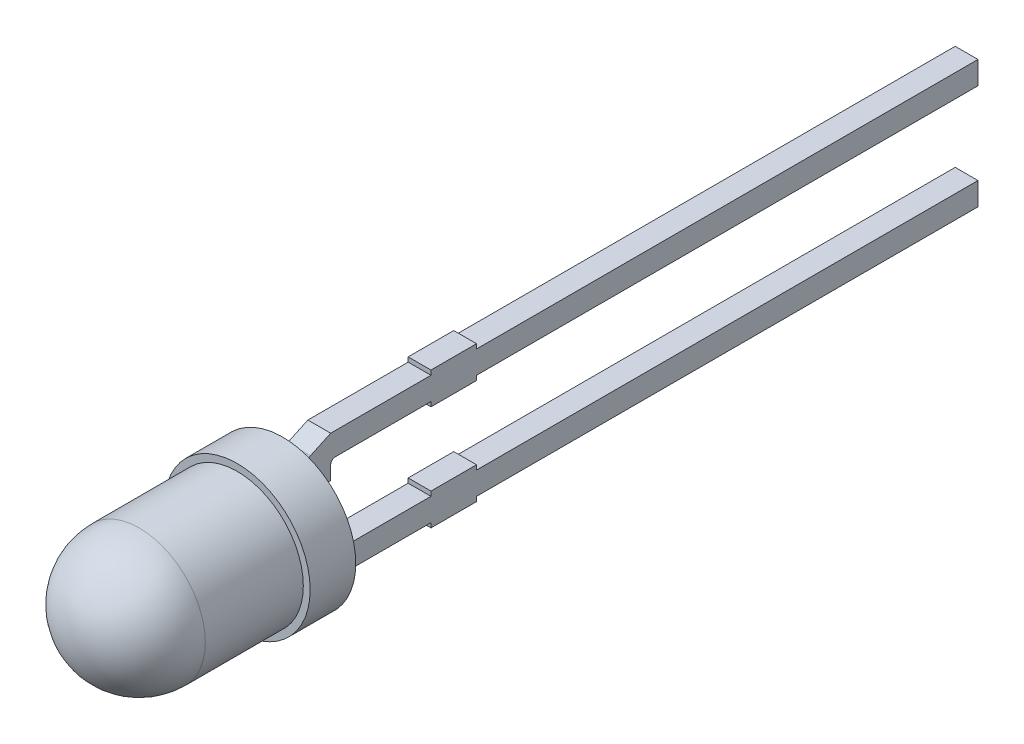
SolidWorks part; units mm, degrees
ref_plane "Front" through (0, 0, 0) normal (0, 0, 1) x (1, 0, 0)
ref_plane "Top" through (0, 0, 0) normal (0, 1, 0) x (1, 0, 0)
ref_plane "Right" through (0, 0, 0) normal (1, 0, 0) x (0, 0, -1)
sketch "Sketch1" plane through (0, 0, 0) normal (1, 0, 0) x (0, 0, -1)
  line L0 (0, 0) -> (76.2974, 0) construction
  line L1 (0, 1.45) -> (2.15, 1.45)
  line L2 (2.15, 1.45) -> (2.15, 1.6)
  line L3 (2.15, 1.6) -> (3.15, 1.6)
  line L4 (3.15, 1.6) -> (3.15, 0)
  line L5 (3.15, 0) -> (-1.45, 0)
  arc A0 (0, 1.45) -> (-1.45, 0) centre (0, 0) ccw
  dimension "D1" = 1.45
  dimension "D2" = 4.6
  dimension "D3" = 1
  dimension "D4" = 1.6
revolve "Revolve1" add sketch "Sketch1" angle 360 about L0
sketch "Sketch2" plane through (0, 0, 0) normal (1, 0, 0) x (0, 0, -1)
  line L0 (3.15, -1.6) -> (3.15, 1.6) construction
  line L1 (3.15, -1.6) -> (3.15, 1.6) construction
  line L2 (3.15, 1.027) -> (3.95, 1.4)
  line L3 (3.95, 1.4) -> (6.15, 1.4)
  line L4 (6.15, 1.4) -> (6.15, 1.5)
  line L5 (6.15, 1.5) -> (7.15, 1.5)
  line L6 (7.15, 1.5) -> (7.15, 1.4)
  line L7 (7.15, 1.4) -> (30.15, 1.4)
  line L8 (30.15, 1.4) -> (30.15, 0.9)
  line L9 (30.15, 0.9) -> (7.15, 0.9)
  line L10 (7.15, 0.9) -> (7.15, 0.8)
  line L11 (7.15, 0.8) -> (6.15, 0.8)
  line L12 (6.15, 0.8) -> (6.15, 0.9)
  line L13 (6.15, 0.9) -> (4.05, 0.9)
  line L14 (3.95, 0.8) -> (3.95, 0.5)
  line L15 (3.95, 0.5) -> (3.15, 0.5)
  line L16 (3.15, 0) -> (7.9733, 0) construction
  line L17 (3.15, 1.027) -> (3.15, 0.5)
  line L18 (3.95, -0.8) -> (3.95, -0.5)
  line L19 (6.15, -0.9) -> (4.05, -0.9)
  line L20 (6.15, -0.8) -> (6.15, -0.9)
  line L21 (7.15, -0.8) -> (6.15, -0.8)
  line L22 (7.15, -0.9) -> (7.15, -0.8)
  line L23 (30.15, -0.9) -> (7.15, -0.9)
  line L24 (30.15, -1.4) -> (30.15, -0.9)
  line L25 (7.15, -1.4) -> (30.15, -1.4)
  line L26 (7.15, -1.5) -> (7.15, -1.4)
  line L27 (6.15, -1.5) -> (7.15, -1.5)
  line L28 (6.15, -1.4) -> (6.15, -1.5)
  line L29 (3.95, -1.4) -> (6.15, -1.4)
  line L30 (3.15, -1.027) -> (3.95, -1.4)
  line L31 (3.15, -1.027) -> (3.15, -0.5)
  line L32 (3.95, -0.5) -> (3.15, -0.5)
  arc A0 (4.05, 0.9) -> (3.95, 0.8) centre (4.05, 0.8) ccw
  arc A1 (4.05, -0.9) -> (3.95, -0.8) centre (4.05, -0.8) cw
  point P19 (3.15, 0)
  dimension "D1" = 0.5
  dimension "D2" = 0.7
  dimension "D3" = 1.4
  dimension "D4" = 0.8
  dimension "D5" = 27
  dimension "D6" = 115
  dimension "D7" = 4
  dimension "D8" = 1
  dimension "D9" = 0.5
  dimension "D10" = 0.1
extrude "Extrude1" add sketch "Sketch2" along normal mid plane 0.5
fillet "Fillet1" radius 0.25 8 edges at (0, -0.5, -3.15) (0, -1.027, -3.15) (-0.25, -0.7635, -3.15) (0, 0.5, -3.15) (-0.25, 0.7635, -3.15) (0, 1.027, -3.15) (0.25, 0.7635, -3.15) (0.25, -0.7635, -3.15)
sketch "Sketch3" plane through (0, 0, 0) normal (1, 0, 0) x (0, 0, -1)
  line L0 (18.15, 1.4) -> (18.15, -1.4)
  line L1 (30.15, 1.4) -> (7.15, 1.4) construction
  line L2 (7.15, -1.4) -> (30.15, -1.4) construction
  line L3 (18.15, -1.4) -> (31.0324, -1.4)
  line L4 (31.0324, -1.4) -> (31.0324, 1.4)
  line L5 (31.0324, 1.4) -> (18.15, 1.4)
  line L6 (3.15, -1.6) -> (3.15, 1.6) construction
  dimension "D1" = 15
extrude "Cut-Extrude1" cut sketch "Sketch3" against normal through all both and the other way through all
